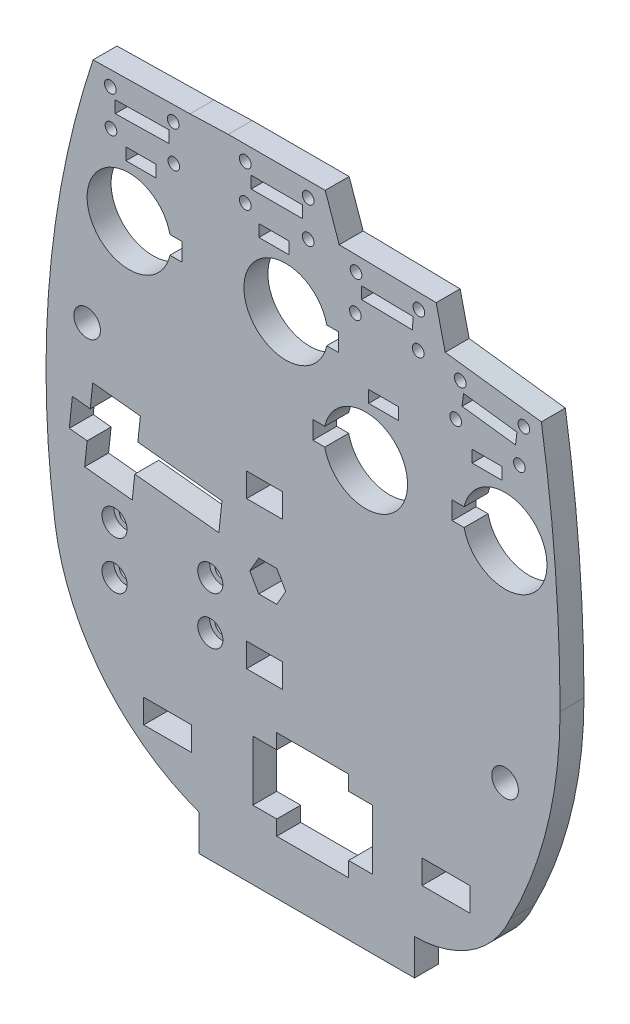
SolidWorks part; units mm, degrees
ref_plane "Front Plane" through (0, 0, 0) normal (0, 0, 1) x (1, 0, 0)
ref_plane "Top Plane" through (0, 0, 0) normal (0, 1, 0) x (1, 0, 0)
ref_plane "Right Plane" through (0, 0, 0) normal (1, 0, 0) x (0, 0, -1)
sketch "Sketch1" plane through (0, 0, 0) normal (0, 0, 1) x (1, 0, 0)
  line L0 (-4.275, 78.51) -> (-4.275, 76.51)
  line L1 (4.275, 78.51) -> (-4.275, 78.51)
  line L2 (-12.9786, -18) -> (-12.9786, -24)
  line L3 (-9.666, 24.0723) -> (-9.153, 28.9531)
  line L4 (-4.275, 76.51) -> (4.275, 76.51)
  line L5 (4.275, 76.51) -> (4.275, 78.51)
  line L6 (-34.6568, 26.6989) -> (-34.1438, 31.5798)
  line L7 (10.3588, 63.1512) -> (10.3588, 60.1512)
  line L8 (-8.1, 82.51) -> (8.1, 82.51)
  line L9 (8.3588, 63.1512) -> (10.3588, 63.1512)
  line L10 (10.4412, 75.8064) -> (26.6388, 75.5236)
  line L11 (32.6473, 57.3216) -> (37.6473, 57.3216)
  line L12 (0, 0) -> (-22.59, 0) construction
  line L13 (10.3588, 60.1512) -> (8.3588, 60.1512)
  line L14 (-17.8416, 63.1512) -> (-15.8416, 63.1512)
  line L15 (-15.8416, 63.1512) -> (-15.8416, 60.1512)
  line L16 (-15.8416, 60.1512) -> (-17.8416, 60.1512)
  line L17 (32.6473, 55.3216) -> (37.6473, 55.3216)
  line L18 (37.6473, 55.3216) -> (37.6473, 57.3216)
  line L19 (32.6473, 57.3216) -> (32.6473, 55.3216)
  line L20 (-27.0195, 78.062) -> (-18.0208, 78.2192)
  line L21 (-27.0195, 78.062) -> (-26.9845, 76.0623)
  line L22 (-10.0543, 52.8756) -> (-18.0543, 52.8756) construction
  line L23 (-9.153, 28.9531) -> (-23.2041, 30.43)
  line L24 (-26.9845, 76.0623) -> (-17.9858, 76.2195)
  line L25 (-24.1352, 21.571) -> (-32.0914, 22.4072)
  line L26 (-32.0914, 22.4072) -> (-31.6733, 26.3853)
  line L27 (-23.7171, 25.5491) -> (-9.666, 24.0723)
  line L28 (-17.9858, 76.2195) -> (-18.0208, 78.2192)
  line L29 (15.3631, 57.3216) -> (20.3631, 57.3216)
  line L30 (15.3631, 55.3216) -> (20.3631, 55.3216)
  line L31 (-12.9786, -24) -> (23.0214, -24)
  line L32 (20.3631, 55.3216) -> (20.3631, 57.3216)
  line L33 (23.0214, -24) -> (23.0214, -18)
  line L34 (15.3631, 57.3216) -> (15.3631, 55.3216)
  line L35 (-2.9786, 72.1512) -> (2.0214, 72.1512)
  line L36 (14.1958, 71.7402) -> (14.1609, 69.7405)
  line L37 (14.1609, 69.7405) -> (22.7096, 69.5913)
  line L38 (8.0257, 48.3216) -> (6.0257, 48.3216)
  line L39 (-2.9786, 70.1512) -> (2.0214, 70.1512)
  line L40 (22.7445, 71.591) -> (14.1958, 71.7402)
  line L41 (6.0257, 48.3216) -> (6.0257, 45.3216)
  line L42 (22.7096, 69.5913) -> (22.7445, 71.591)
  line L43 (-22.59, 0) -> (-22.59, 82.14) construction
  line L44 (2.0214, 70.1512) -> (2.0214, 72.1512)
  line L45 (18.54, 75.665) -> (18.5934, 78.7251) construction
  line L46 (-2.9786, 72.1512) -> (-2.9786, 70.1512)
  line L47 (40.1436, 63.5476) -> (31.2139, 64.6755)
  line L48 (6.0257, 45.3216) -> (8.0257, 45.3216)
  line L49 (29.3099, 45.3216) -> (31.3099, 45.3216)
  line L50 (29.3099, 48.3216) -> (29.3099, 45.3216)
  line L51 (31.3099, 48.3216) -> (29.3099, 48.3216)
  line L52 (-22.786, 34.408) -> (-30.7422, 35.2443)
  line L53 (31.2139, 64.6755) -> (30.9632, 62.6912)
  line L54 (-25.179, 72.1512) -> (-20.179, 72.1512)
  line L55 (-30.6888, 81.9985) -> (-14.4912, 82.2815)
  line L56 (44.2162, 67.065) -> (28.1438, 69.095)
  line L57 (-25.179, 70.1512) -> (-20.179, 70.1512)
  line L58 (30.9632, 62.6912) -> (39.893, 61.5633)
  line L59 (-20.179, 70.1512) -> (-20.179, 72.1512)
  line L60 (-25.179, 72.1512) -> (-25.179, 70.1512)
  line L61 (39.893, 61.5633) -> (40.1436, 63.5476)
  line L62 (-34.6568, 26.6989) -> (-31.6733, 26.3853)
  line L63 (-4, -2.5) -> (0, -2.5)
  line L64 (12, 0) -> (0, 0)
  line L65 (12, 0) -> (12, -2.5)
  line L66 (12, -15) -> (0, -15)
  line L67 (-30.7422, 35.2443) -> (-31.1603, 31.2662)
  line L68 (-23.2041, 30.43) -> (-22.786, 34.408)
  line L69 (-34.1438, 31.5798) -> (-31.1603, 31.2662)
  line L70 (-24.1352, 21.571) -> (-23.7171, 25.5491)
  line L71 (16, -7.5) -> (38.9913, -7.5) construction
  line L72 (0, -15) -> (0, -12.5)
  line L73 (-4, -12.5) -> (-4, -2.5)
  line L74 (-4, -12.5) -> (0, -12.5)
  line L75 (0, -2.5) -> (0, 0)
  line L76 (0, 0) -> (0, 82.51) construction
  line L77 (-22.0543, 52.8756) -> (-27.0543, 52.8756) construction
  line L78 (-10.0543, -2.1244) -> (-18.0543, -2.1244) construction
  line L79 (-22.0543, -2.1244) -> (-27.0543, -2.1244) construction
  line L80 (0, 0) -> (18.54, 0) construction
  line L81 (16, -12.5) -> (12, -12.5)
  line L82 (16, -12.5) -> (16, -2.5)
  line L83 (16, -2.5) -> (12, -2.5)
  line L84 (12, -12.5) -> (12, -15)
  line L85 (-9.4095, 26.5127) -> (6.8489, 24.8039) construction
  line L86 (0, 23.7547) -> (-3, 23.7547)
  line L87 (-3, 23.7547) -> (-4.5, 21.1566)
  line L88 (-4.5, 21.1566) -> (-3, 18.5585)
  line L89 (18.54, 0) -> (18.54, 75.665) construction
  line L90 (0, 0) -> (36.18, 0) construction
  line L91 (36.18, 0) -> (36.18, 68.08) construction
  line L92 (28.1438, 69.095) -> (26.6388, 75.5236)
  line L93 (10.4412, 75.8064) -> (8.1, 82.51)
  line L94 (-8.1, 82.51) -> (-14.4912, 82.2815)
  line L95 (-34.6568, 26.6989) -> (47.3354, 26.6989) construction
  line L96 (35.6788, 64.1115) -> (36.18, 68.08) construction
  line L97 (-3, 18.5585) -> (0, 18.5585)
  line L98 (0, 18.5585) -> (1.5, 21.1566)
  line L99 (1.5, 21.1566) -> (0, 23.7547)
  line L100 (0, 18.5585) -> (-3, 23.7547) construction
  line L101 (0, 23.7547) -> (-3, 18.5585) construction
  line L102 (38.1473, 11.8216) -> (-37.0527, 11.8216) construction
  line L103 (-27.7956, 79.5486) -> (-30.6451, 79.4989) construction
  line L104 (0.9634, 10.717) -> (0.9634, 6.717)
  line L105 (0.9634, 6.717) -> (-5.0366, 6.717)
  line L106 (-5.0366, 6.717) -> (-5.0366, 10.717)
  line L107 (-5.0366, 10.717) -> (0.9634, 10.717)
  line L108 (-5.0366, 31.3356) -> (0.9634, 31.3356)
  line L109 (-5.0366, 35.3356) -> (-5.0366, 31.3356)
  line L110 (0.9634, 35.3356) -> (-5.0366, 35.3356)
  line L111 (0.9634, 31.3356) -> (0.9634, 35.3356)
  line L112 (-30.6451, 79.4989) -> (-30.6888, 81.9985) construction
  line L113 (-17.2971, 79.732) -> (-14.4475, 79.7819) construction
  line L114 (-14.4475, 79.7819) -> (-14.4912, 82.2815) construction
  line L115 (-22.5201, 78.1406) -> (-22.59, 82.14) construction
  line L116 (5.25, 80.01) -> (8.1, 80.01) construction
  line L117 (8.1, 80.01) -> (8.1, 82.51) construction
  line L118 (-5.25, 80.01) -> (-8.1, 80.01) construction
  line L119 (-22.0543, 0.1006) -> (-27.0543, 0.1006) construction
  line L120 (-8.1, 80.01) -> (-8.1, 82.51) construction
  line L121 (-10.0543, 1.8756) -> (-10.0543, -2.1244) construction
  line L122 (30.6581, 66.2576) -> (27.8306, 66.6147) construction
  line L123 (-10.0543, 52.8756) -> (-10.0543, 46.8756) construction
  line L124 (-10.0543, 1.8756) -> (-18.0543, 1.8756) construction
  line L125 (-18.0543, 1.8756) -> (-18.0543, -2.1244) construction
  line L126 (27.8306, 66.6147) -> (28.1438, 69.095) construction
  line L127 (13.2472, 73.257) -> (10.3976, 73.3067) construction
  line L128 (-22.0543, 0.1006) -> (-22.0543, -2.1244) construction
  line L129 (-27.0543, 0.1006) -> (-27.0543, -2.1244) construction
  line L130 (30.6581, 66.2576) -> (29.9062, 60.3049) construction
  line L131 (-10.0543, 46.8756) -> (-18.0543, 46.8756) construction
  line L132 (-27.0543, 52.8756) -> (-27.0543, 50.6506) construction
  line L133 (-18.0543, 46.8756) -> (-18.0543, 52.8756) construction
  line L134 (10.4412, 75.8064) -> (10.3976, 73.3067) construction
  line L135 (-22.0543, 6.717) -> (-22.0543, 10.717) construction
  line L136 (-22.0543, 10.717) -> (-27.0543, 10.717) construction
  line L137 (-27.0543, 50.6506) -> (-22.0543, 50.6506) construction
  line L138 (-22.0543, 52.8756) -> (-22.0543, 50.6506) construction
  line L139 (-27.0543, 10.717) -> (-27.0543, 6.717) construction
  line L140 (-27.0543, 6.717) -> (-22.0543, 6.717) construction
  line L141 (-27.0543, 38.7272) -> (-22.0543, 38.7272) construction
  line L142 (-22.0543, 38.7272) -> (-22.0543, 42.7272) construction
  line L143 (-22.0543, 42.7272) -> (-27.0543, 42.7272) construction
  line L144 (-27.0543, 42.7272) -> (-27.0543, 38.7272) construction
  line L145 (23.7456, 73.0738) -> (26.5951, 73.024) construction
  line L146 (26.5951, 73.024) -> (26.6388, 75.5236) construction
  line L147 (41.2989, 64.9136) -> (44.1265, 64.5564) construction
  line L148 (41.2989, 64.9136) -> (40.547, 58.9609) construction
  line L149 (40.547, 58.9609) -> (43.3746, 58.6037) construction
  line L150 (43.3746, 58.6037) -> (44.1265, 64.5564) construction
  line L151 (23.7456, 73.0738) -> (23.6409, 67.0747) construction
  line L152 (13.2472, 73.257) -> (13.1425, 67.2579) construction
  line L153 (-17.2971, 79.732) -> (-17.1923, 73.733) construction
  line L154 (-27.7956, 79.5486) -> (-27.6908, 73.5496) construction
  line L155 (38.1473, 46.8216) -> (38.1473, 11.8216) construction
  line L156 (-31.6, 35.8756) -> (-31.6, -2.1244) construction
  line L157 (-31.6, -2.1244) -> (-6.6, -2.1244) construction
  line L158 (-6.6, -2.1244) -> (-6.6, 35.8756) construction
  line L159 (-6.6, 35.8756) -> (-31.6, 35.8756) construction
  arc A0 (-37.0527, 11.8216) -> (-30.6888, 81.9985) centre (116.3395, 33.2885) cw
  circle A1 centre (-1.5, 21.1566) radius 4.5 construction
  arc A2 (8.3588, 63.1512) -> (8.3588, 60.1512) centre (1.5214, 61.6512) ccw
  arc A3 (8.0257, 45.3216) -> (8.0257, 48.3216) centre (14.8631, 46.8216) ccw
  arc A4 (-17.8416, 63.1512) -> (-17.8416, 60.1512) centre (-24.679, 61.6512) ccw
  arc A5 (31.3099, 45.3216) -> (31.3099, 48.3216) centre (38.1473, 46.8216) ccw
  arc A6 (23.0214, -18) -> (38.9913, -7.5) centre (23.0214, -0.6053) ccw
  arc A7 (47.3354, 26.6989) -> (38.9913, -7.5) centre (-26.9196, 26.6989) cw
  arc A8 (-37.0527, 11.8216) -> (-12.9786, -18) centre (-0.147, 16.9865) ccw
  arc A9 (47.3354, 26.6989) -> (44.2162, 67.065) centre (-215.4084, 26.6989) ccw
  circle A10 centre (-27.1, 24.8756) radius 1.225 construction
  circle A11 centre (38.1473, 11.8216) radius 2.225
  circle A12 centre (-14, -9.1244) radius 2.225 construction
  circle A13 centre (-27.1, 8.8756) radius 1.225
  circle A14 centre (-27.1, 16.8756) radius 1.225
  circle A15 centre (-11.1, 8.8756) radius 1.225
  circle A16 centre (-11.1, 16.8756) radius 1.225
  circle A17 centre (-11.1, 24.8756) radius 1.225 construction
  circle A18 centre (-5.25, 80.01) radius 0.975
  circle A19 centre (30.6581, 66.2576) radius 0.975
  circle A22 centre (-31.6815, 43.4564) radius 2.225
  circle A49 centre (5.25, 80.01) radius 0.975
  circle A50 centre (5.25, 74.01) radius 0.975
  circle A51 centre (-5.25, 74.01) radius 0.975
  circle A52 centre (-27.7956, 79.5486) radius 0.975
  circle A53 centre (-17.2971, 79.732) radius 0.975
  circle A54 centre (-27.6908, 73.5496) radius 0.975
  circle A55 centre (-17.1923, 73.733) radius 0.975
  circle A56 centre (23.6409, 67.0747) radius 0.975
  circle A57 centre (13.1425, 67.2579) radius 0.975
  circle A58 centre (23.7456, 73.0738) radius 0.975
  circle A59 centre (13.2472, 73.257) radius 0.975
  circle A60 centre (29.9062, 60.3049) radius 0.975
  circle A61 centre (41.2989, 64.9136) radius 0.975
  circle A63 centre (40.547, 58.9609) radius 0.975
  dimension "D1" = 4.45
  dimension "D2" = 1.95
  dimension "D11" = 1.5214
  dimension "D12" = 2.0214
  dimension "D16" = 6.0257
  dimension "D17" = 4
  dimension "D18" = 8.3588
  dimension "D19" = 22.59
  dimension "D22" = 4
  dimension "D23" = 18.54
  dimension "D24" = 75.665
  dimension "D25" = 12
  dimension "D35" = 4
  dimension "D36" = 16.2
  dimension "D37" = 2
  dimension "D38" = 29.3099
  dimension "D39" = 2.85
  dimension "D40" = 46.8216
  dimension "D43" = 2.85
  dimension "D44" = 24.679
  dimension "D45" = 9
  dimension "D46" = 0.7292
  dimension "D47" = 4.9078
  dimension "D49" = 5.0366
  dimension "D51" = 9.666
  dimension "D55" = 24
  dimension "D56" = 15.8416
  dimension "D13" = 4
  dimension "D58" = 2.5
  dimension "D59" = 18.0543
  dimension "D60" = 8.1
  dimension "D61" = 6
  dimension "D63" = 22.0543
  dimension "D65" = 2.85
  dimension "D52" = 10.0543
  dimension "D48" = 25.1285
  dimension "D53" = 12.9786
  dimension "D57" = 4
  dimension "D69" = 6
  dimension "D70" = 2.5
  dimension "D71" = 1.8756
  dimension "D79" = 43.4564
  dimension "D82" = 55.3216
  dimension "D67" = 2.5
  dimension "D68" = 31.6815
  dimension "D92" = 8
  dimension "D5" = 7
  dimension "D29" = 2.5
  dimension "D83" = 8.1
  dimension "D85" = 2
  dimension "D87" = 38
  dimension "D89" = 2.45
  dimension "D10" = 0.9634
  dimension "D14" = 82.51
  dimension "D15" = 3
  dimension "D20" = 10
  dimension "D21" = 82.14
  dimension "D26" = 15.3631
  dimension "D27" = 2.5
  dimension "D28" = 0
  dimension "D30" = 20.3631
  dimension "D31" = 36.18
  dimension "D32" = 68.08
  dimension "D33" = 23.0214
  dimension "D34" = 6
  dimension "D41" = 14.8631
  dimension "D42" = 32.6473
  dimension "D50" = 9.153
  dimension "D54" = 14
  dimension "D62" = 20.179
  dimension "D66" = 2.85
  dimension "D72" = 6.717
  dimension "D73" = 9.0001
  dimension "D74" = 9.0007
  dimension "D75" = 35
  dimension "D76" = 21.571
  dimension "D77" = 31.3356
  dimension "D78" = 6
  dimension "D80" = 45.3216
  dimension "D81" = 46.8756
  dimension "D84" = 60.1512
  dimension "D86" = 70.1512
  dimension "D88" = 25
  dimension "D90" = 6.6
  dimension "D91" = 2.1244
  dimension "D93" = 9.1244
  dimension "D94" = 16
  dimension "D95" = 8
  dimension "D96" = 4.5
  dimension "D97" = 2
extrude "Boss-Extrude1" add sketch "Sketch1" along normal blind 4
sketch "Sketch2" plane through (0, 0, 4) normal (0, 0, 1) x (1, 0, 0)
  line L1 (-19.1, 16.8756) -> (-19.1, 8.8756) construction
  circle A0 centre (-11.1, 16.8756) radius 2.1
  circle A1 centre (-11.1, 8.8756) radius 2.1
  circle A2 centre (-27.1, 8.8756) radius 2.1
  circle A3 centre (-27.1, 16.8756) radius 2.1
  dimension "D1" = 4.2
  dimension "D2" = 27.1
extrude "Cut-Extrude1" cut sketch "Sketch2" against normal blind 2
sketch "Sketch3" plane through (0, 0, 0) normal (0, 0, -1) x (-1, 0, 0)
  line L1 (-24.2714, -10) -> (-32.2714, -10)
  line L2 (-32.2714, -10) -> (-32.2714, -6)
  line L3 (-32.2714, -6) -> (-24.2714, -6)
  line L4 (-24.2714, -6) -> (-24.2714, -10)
  line L5 (-5.0214, -24) -> (-5.0214, -4.0378) construction
  line L6 (12.9786, -24) -> (-23.0214, -24) construction
  line L7 (14.2286, -6) -> (14.2286, -10)
  line L8 (22.2286, -6) -> (14.2286, -6)
  line L9 (22.2286, -10) -> (22.2286, -6)
  line L10 (14.2286, -10) -> (22.2286, -10)
  dimension "D1" = 4
  dimension "D2" = 8
  dimension "D3" = 14
  dimension "D4" = 19.25
extrude "Cut-Extrude2" cut sketch "Sketch3" against normal through all
equation "\"D14@Sketch1\"= \"HL@parametersSketch@prostheticParameters.SLDPRT\" * 0.446'Mioddle Base Frame "
equation "\"D19@Sketch1\"= \"HB@parametersSketch@prostheticParameters.SLDPRT\" * 0.251'Index Base Frame X"
equation "\"D21@Sketch1\"= \"HL@parametersSketch@prostheticParameters.SLDPRT\" * 0.444'Index Base Frame Y"
equation "\"D23@Sketch1\"= \"HB@parametersSketch@prostheticParameters.SLDPRT\" * 0.206'Ring Base Frame X"
equation "\"D24@Sketch1\"= \"HL@parametersSketch@prostheticParameters.SLDPRT\" * 0.409'Ring Base Frame Y"
equation "\"D31@Sketch1\"= \"HB@parametersSketch@prostheticParameters.SLDPRT\" * 0.402'Pinky Base Frame X"
equation "\"D32@Sketch1\"= \"HL@parametersSketch@prostheticParameters.SLDPRT\" * 0.368'Pinky Base Frame Y"
equation "\"D36@Sketch1\"= \"fingerWidth@parametersSketch@prostheticParameters.SLDPRT\"'Fingers Width"
equation "\"D76@Sketch1\"= \"HL@parametersSketch@prostheticParameters.SLDPRT\" * 0.1166'Hole Thumb Y"
equation "\"D51@Sketch1\"= \"HB@parametersSketch@prostheticParameters.SLDPRT\" * 0.1074'Hole Thumb X1"
equation "\"D50@Sketch1\" = \"HB@parametersSketch@prostheticParameters.SLDPRT\" * 0.1017'Hole Thumb X2"
equation "\"D73@Sketch1\"=(\"fingerWidth@parametersSketch@prostheticParameters.SLDPRT\" * 0.55556)"
equation "\"D74@Sketch1\"=(\"fingerWidth@parametersSketch@prostheticParameters.SLDPRT\" * 0.5556)"
equation "\"D60@Sketch1\"= \"fingerWidth@parametersSketch@prostheticParameters.SLDPRT\" / 2"
equation "\"D83@Sketch1\"= \"fingerWidth@parametersSketch@prostheticParameters.SLDPRT\" / 2"
